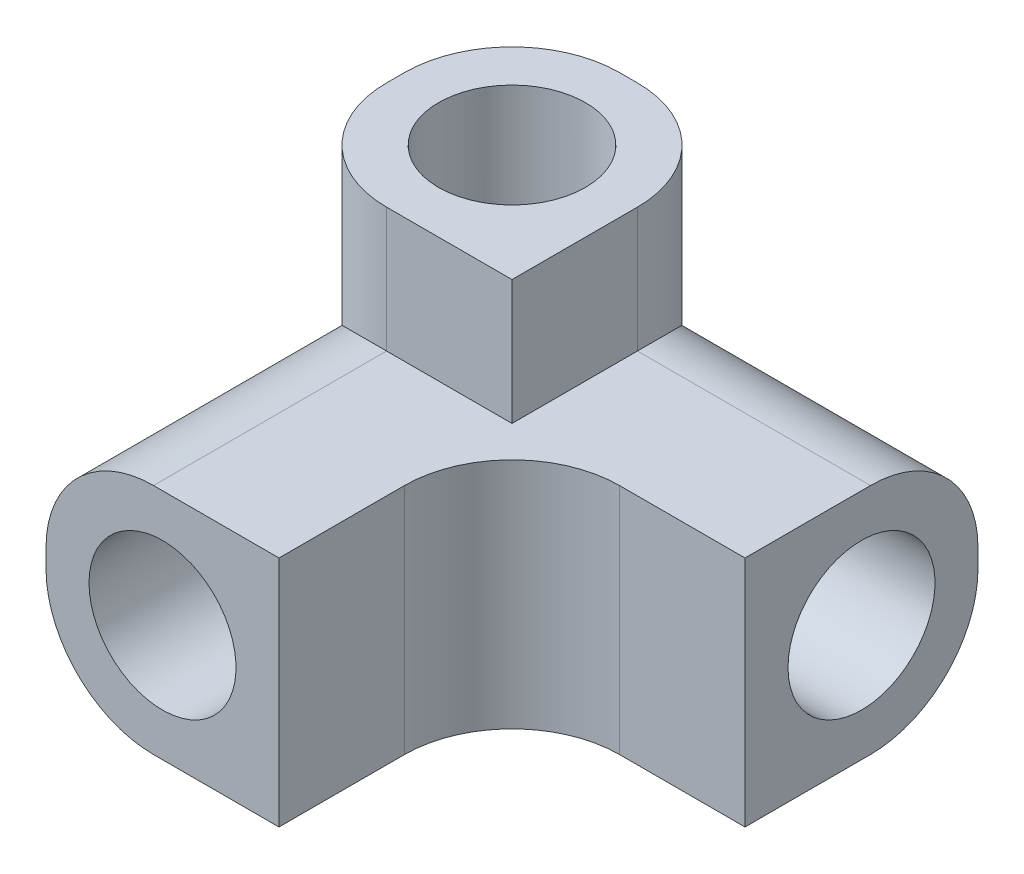
SolidWorks part; units mm, degrees
ref_plane "前视基准面" through (0, 0, 0) normal (0, 0, 1) x (1, 0, 0)
ref_plane "上视基准面" through (0, 0, 0) normal (0, 1, 0) x (1, 0, 0)
ref_plane "右视基准面" through (0, 0, 0) normal (1, 0, 0) x (0, 0, -1)
sketch "草图1" plane through (0, 0, 0) normal (0, 0, 1) x (1, 0, 0)
  line L1 (-11.8307, 8.0321) -> (-5.3307, 8.0321)
  line L2 (-11.8307, 8.0321) -> (-11.8307, 1.5321)
  line L3 (-11.8307, 1.5321) -> (-5.3307, 1.5321)
  line L4 (-5.3307, 8.0321) -> (-5.3307, 1.5321)
  line L5 (-11.8307, 8.0321) -> (-5.3307, 1.5321) construction
  line L6 (-11.8307, 1.5321) -> (-5.3307, 8.0321) construction
  circle A1 centre (-8.5807, 4.7821) radius 2.05
  dimension "D1" = 4.1
  dimension "D2" = 6.5
  dimension "D3" = 6.5
extrude "凸台-拉伸1" add sketch "草图1" along normal blind 6.5
sketch "草图2" plane through (-5.3307, 0, 0) normal (1, 0, 0) x (0, 0, -1)
  line L0 (-6.5, 8.0321) -> (0, 8.0321) construction
  line L1 (0, 1.5321) -> (6.5, 1.5321)
  line L2 (0, 1.5321) -> (0, 14.5321)
  line L3 (0, 14.5321) -> (6.5, 14.5321)
  line L4 (6.5, 1.5321) -> (6.5, 14.5321)
  dimension "D1" = 6.5
  dimension "D2" = 6.5
extrude "凸台-拉伸2" add sketch "草图2" against normal up to surface (6.5 mm away) up to face at (-11.8307, 4.7821, 3.25)
sketch "草图3" plane through (-5.3307, 0, 0) normal (1, 0, 0) x (0, 0, -1)
  line L0 (6.5, 8.0321) -> (0, 1.5321) construction
  line L1 (0, 8.0321) -> (6.5, 8.0321)
  line L2 (0, 8.0321) -> (0, 1.5321)
  line L3 (0, 1.5321) -> (6.5, 1.5321)
  line L4 (6.5, 8.0321) -> (6.5, 1.5321)
  line L5 (0, 8.0321) -> (6.5, 1.5321) construction
  circle A0 centre (3.25, 4.7821) radius 2.05
  dimension "D1" = 4.1
extrude "凸台-拉伸3" add sketch "草图3" along normal blind 6.5
sketch "草图4" plane through (0, 14.5321, 0) normal (0, 1, 0) x (1, 0, 0)
  line L0 (-11.8307, 0) -> (-5.3307, 6.5) construction
  line L1 (-5.3307, 0) -> (-11.8307, 6.5) construction
  circle A0 centre (-8.5807, 3.25) radius 2.05
  dimension "D1" = 4.1
extrude "切除-拉伸1" cut sketch "草图4" against normal blind 8
fillet "圆角1" radius 3 7 edges at (-5.3307, 11.2821, -6.5) (-11.8307, 11.2821, 0) (-11.8307, 8.0321, 3.25) (-2.0807, 8.0321, -6.5) (-5.3307, 1.5321, -6.5) (-11.8307, 1.5321, 0) (-11.8307, 8.0321, -6.5)
fillet "圆角2" radius 3 1 edges at (-5.3307, 4.7821, 0)
sketch "草图5" plane through (-5.3307, 0, 0) normal (1, 0, 0) x (0, 0, -1)
  line L0 (0, 14.5321) -> (0, 8.0321) construction
  line L1 (0, 11.5088) -> (7.5428, 11.5088)
  line L2 (0, 11.5088) -> (0, 15.445)
  line L3 (0, 15.445) -> (7.5428, 15.445)
  line L4 (7.5428, 11.5088) -> (7.5428, 15.445)
extrude "切除-拉伸2" cut sketch "草图5" against normal through all both and the other way through all
